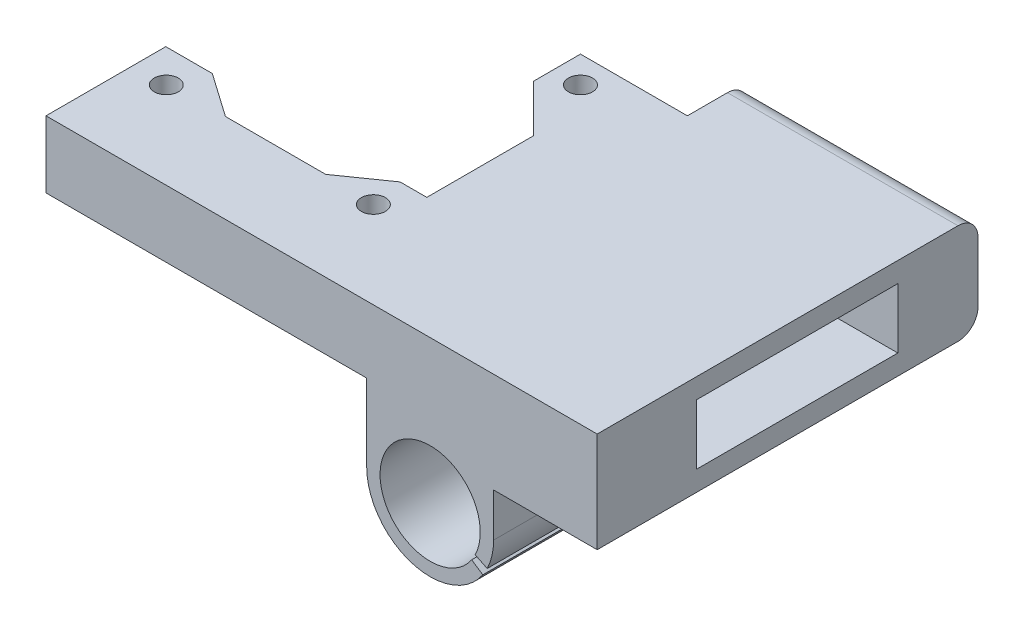
SolidWorks part; units mm, degrees
ref_plane "Front Plane" through (0, 0, 0) normal (0, 0, 1) x (1, 0, 0)
ref_plane "Top Plane" through (0, 0, 0) normal (0, 1, 0) x (1, 0, 0)
ref_plane "Right Plane" through (0, 0, 0) normal (1, 0, 0) x (0, 0, -1)
sketch "Sketch1" plane through (0, 0, 0) normal (0, 1, 0) x (1, 0, 0)
  line L0 (0, 0) -> (82.5, 0)
  line L1 (82.5, 0) -> (82.5, 57)
  line L2 (82.5, 57) -> (48, 57)
  line L3 (48, 57) -> (48, 48)
  line L4 (48, 48) -> (32, 48)
  line L5 (32, 48) -> (32, 41)
  line L6 (32, 41) -> (39.0711, 33.9289)
  line L7 (39.0711, 33.9289) -> (39.0711, 17.9289)
  line L8 (39.0711, 17.9289) -> (35.0711, 17.9289)
  line L9 (35.0711, 17.9289) -> (28.5179, 13.3403)
  line L10 (28.5179, 13.3403) -> (13.5179, 13.3403)
  line L11 (13.5179, 13.3403) -> (6.9646, 17.9289)
  line L12 (6.9646, 17.9289) -> (0, 17.9289)
  line L13 (0, 17.9289) -> (0, 0)
  line L14 (36, 44) -> (36, 13) construction
  line L15 (36, 13) -> (5, 13) construction
  circle A0 centre (5, 13) radius 1.8
  circle A1 centre (36, 13) radius 1.8
  circle A2 centre (36, 44) radius 1.8
  dimension "D16" = 3.6
  dimension "D18" = 13
  dimension "D19" = 5
  dimension "D1" = 82.5
  dimension "D2" = 57
  dimension "D3" = 34.5
  dimension "D4" = 9
  dimension "D5" = 16
  dimension "D6" = 7
  dimension "D7" = 10
  dimension "D8" = 135
  dimension "D9" = 16
  dimension "D10" = 4
  dimension "D11" = 8
  dimension "D12" = 145
  dimension "D13" = 15
  dimension "D14" = 8
  dimension "D15" = 145
  dimension "D17" = 31
extrude "Boss-Extrude1" add sketch "Sketch1" along normal blind 31 contours L12 L13 L0 L1 L2 L3 L4 L5 L6 L7 L8 L9 L10 L11 A2 A1 A0 region at (52.7755, 0, -24.1718)
sketch "Sketch2" plane through (0, 0, 0) normal (0, -1, 0) x (1, 0, 0)
  line L0 (82.5, -57) -> (82.5, 0)
  line L1 (82.5, 0) -> (67, 0)
  line L2 (0, 0) -> (82.5, 0) construction
  line L3 (67, 0) -> (67, -48)
  line L4 (67, -48) -> (48, -48)
  line L5 (48, -48) -> (48, -57)
  line L6 (82.5, -57) -> (48, -57) construction
  line L7 (48, -57) -> (82.5, -57)
  dimension "D1" = 15.5
extrude "Cut-Extrude1" cut sketch "Sketch2" against normal blind 16
fillet "Fillet1" radius 3 2 edges at (65.25, 31, -57) (65.25, 16, -57)
sketch "Sketch3" plane through (0, 0, -48) normal (0, 0, -1) x (-1, 0, 0)
  line L0 (-67, 0) -> (-32, 0) construction
  line L1 (-67, 16) -> (-67, 0) construction
  line L2 (-64.241, 6.2122) -> (-66.0385, 5.3355)
  line L3 (-67, 0) -> (-48, 0)
  line L4 (-67, 0) -> (-67, 16)
  line L5 (-67, 16) -> (-48, 16)
  line L6 (-48, 0) -> (-48, 16)
  line L7 (-65.3759, 4.1877) -> (-63.7178, 5.3061)
  line L8 (-64.241, 6.2122) -> (-57.5, 9.5) construction
  line L9 (-57.5, 9.5) -> (-57.5, 0) construction
  circle A0 centre (-57.5, 9.5) radius 9.5
  circle A1 centre (-57.5, 9.5) radius 7.5
  line M1 (-67, 0) -> (-32, 0)
  line M5 (-48, 16) -> (-67, 16)
  dimension "D1" = 19
  dimension "D2" = 15
  dimension "D3" = 8
  dimension "D4" = 64
extrude "Cut-Extrude2" cut sketch "Sketch3" against normal through all both and the other way through all contours A1 M5 | A1 M5 | A0 L4 M1 | A1 L2 A0 L7 | A0 L3 L6 region at (64.8892, 5.2339, -48) region at (57.5, 9.2966, -48) region at (64.878, 2.122, -48) region at (57.5, 16.4024, -48) region at (50.122, 2.122, -48)
sketch "Sketch5" plane through (0, 0, 0) normal (0, -1, 0) x (1, 0, 0)
  line L1 (48, -48) -> (0, -48)
  line L2 (48, -48) -> (48, 0)
  line L3 (48, 0) -> (0, 0)
  line L4 (0, -48) -> (0, 0)
extrude "Cut-Extrude3" cut sketch "Sketch5" against normal blind 21
sketch "Sketch6" plane through (82.5, 0, 0) normal (1, 0, 0) x (0, 0, -1)
  line L0 (45, 23.5) -> (57, 23.5) construction
  line L1 (14.858, 28) -> (45, 28)
  line L2 (14.858, 28) -> (14.858, 19)
  line L3 (14.858, 19) -> (45, 19)
  line L4 (45, 28) -> (45, 19)
  line L6 (57, 28) -> (57, 19) construction
  dimension "D1" = 9
  dimension "D2" = 30.142
  dimension "D3" = 12
extrude "Cut-Extrude4" cut sketch "Sketch6" against normal blind 31.4
sketch "Sketch7" plane through (51.1, 0, 0) normal (1, 0, 0) x (0, 0, -1)
  line L0 (14.858, 19) -> (45, 19) construction
  line L3 (17.9289, 19) -> (38.9289, 19)
  line L4 (17.9289, 19) -> (17.9289, 28)
  line L7 (17.9289, 28) -> (38.9289, 28)
  line L8 (38.9289, 19) -> (38.9289, 28)
  line L9 (45, 28) -> (14.858, 28) construction
  dimension "D1" = 21
extrude "Cut-Extrude5" cut sketch "Sketch7" against normal through all
sketch "Sketch8" plane through (0, 21, 0) normal (0, -1, 0) x (1, 0, 0)
  circle A0 centre (5, -13) radius 3.5
  circle A1 centre (36, -13) radius 3.5
  circle A2 centre (36, -44) radius 3.5
  dimension "D1" = 7
extrude "Cut-Extrude6" cut sketch "Sketch8" against normal blind 1.5
